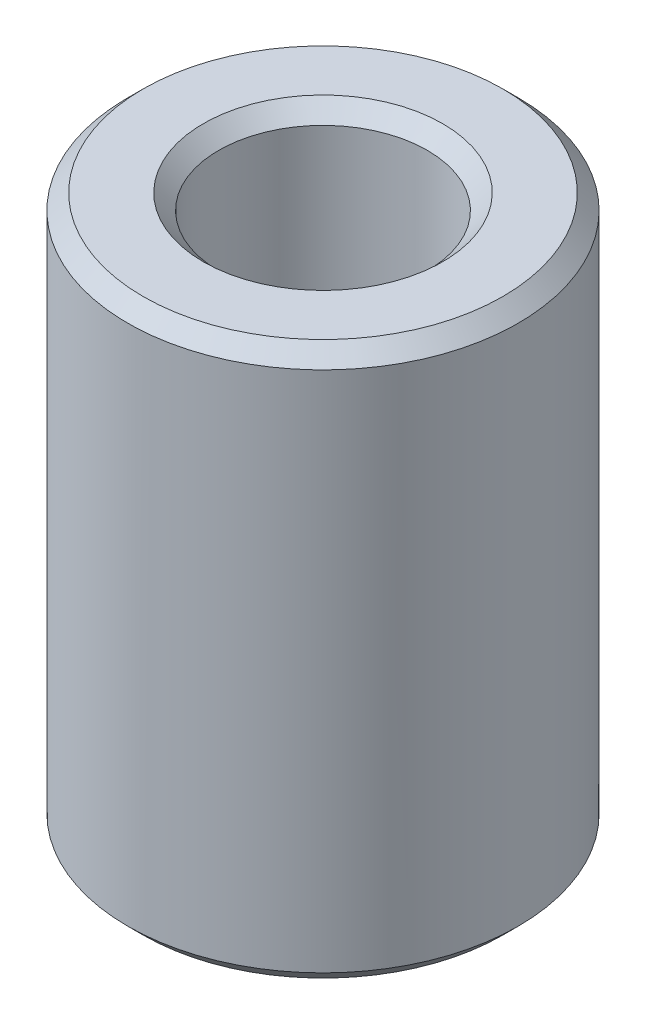
SolidWorks part; units mm, degrees
ref_plane "Front Plane" through (0, 0, 0) normal (0, 0, 1) x (1, 0, 0)
ref_plane "Top Plane" through (0, 0, 0) normal (0, 1, 0) x (1, 0, 0)
ref_plane "Right Plane" through (0, 0, 0) normal (1, 0, 0) x (0, 0, -1)
sketch "Sketch1" plane through (0, 0, 0) normal (0, 1, 0) x (1, 0, 0)
  circle A0 centre (0, 0) radius 45
  dimension "SLEEVE_OD" = 90
extrude "Boss-Extrude1" add sketch "Sketch1" along normal blind 127.4573
sketch "Sketch2" plane through (0, 0, 0) normal (0, 1, 0) x (1, 0, 0)
  circle A0 centre (0, 0) radius 24.0366
  dimension "BORE_D" = 48.0731
extrude "Cut-Extrude1" cut sketch "Sketch2" along normal through all
chamfer "Chamfer1" distance 3.549 angle 45 4 edges at (0, 127.4573, 24.0366) (0, 0, 24.0366) (0, 0, 45) (0, 127.4573, 45)
